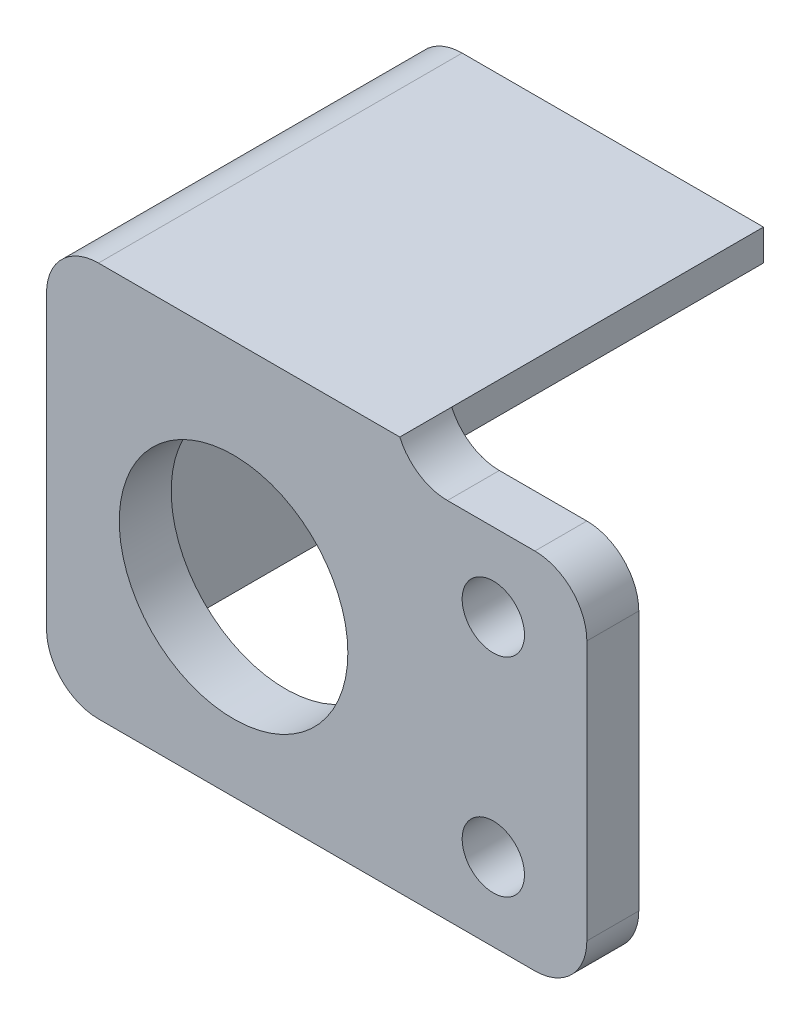
SolidWorks part; units mm, degrees
ref_plane "Front Plane" through (0, 0, 0) normal (0, 0, 1) x (1, 0, 0)
ref_plane "Top Plane" through (0, 0, 0) normal (0, 1, 0) x (1, 0, 0)
ref_plane "Right Plane" through (0, 0, 0) normal (1, 0, 0) x (0, 0, -1)
sketch "Sketch1" plane through (0, 0, 0) normal (0, 0, 1) x (1, 0, 0)
  line L1 (-25, 17.5) -> (25, 17.5)
  line L2 (-25, 17.5) -> (-25, -17.5)
  line L3 (-25, -17.5) -> (25, -17.5)
  line L4 (25, 17.5) -> (25, -17.5)
  circle A0 centre (-9, 0) radius 11
  circle A2 centre (16, -10) radius 3
  circle A3 centre (16, 10) radius 3
  point P0 (0, 0)
extrude "Boss-Extrude1" add sketch "Sketch1" along normal blind 5
sketch "Sketch2" plane through (0, 17.5, 0) normal (0, 1, 0) x (1, 0, 0)
  line L0 (25, -5) -> (7, -5)
  line L1 (25, -5) -> (-25, -5) construction
  line L2 (7, -5) -> (7, 30)
  line L3 (7, -5) -> (-25, -5)
  line L4 (-25, -5) -> (-25, 30)
  line L5 (-25, 30) -> (7, 30)
  line L6 (-25, -5) -> (7, -5)
  line M1 (25, 0) -> (-25, 0)
  line M2 (-25, 0) -> (-25, -5)
  line M3 (-25, -5) -> (25, -5)
extrude "Boss-Extrude2" add sketch "Sketch2" along normal blind 3 contours L5 L4 L2 M1 | L2 M3 M1 M2 region at (-9, 17.5, 2.5) region at (-9, 17.5, -15)
sketch "Sketch3" plane through (-25, 0, 0) normal (-1, 0, 0) x (0, 0, 1)
  line L0 (5, 20.5) -> (-30, 20.5)
  line L1 (5, 20.5) -> (5, -17.5)
  line L2 (-30, 20.5) -> (-30, -17.5)
  line L3 (-30, -17.5) -> (5, -17.5)
extrude "Boss-Extrude3" add sketch "Sketch3" along normal blind 2
fillet "Fillet1" radius 5 6 edges at (25, 17.5, 2.5) (7, 17.5, 2.5) (-27, -17.5, -12.5) (-27, 20.5, -12.5) (25, -17.5, 2.5) (-25, 17.5, -15)
